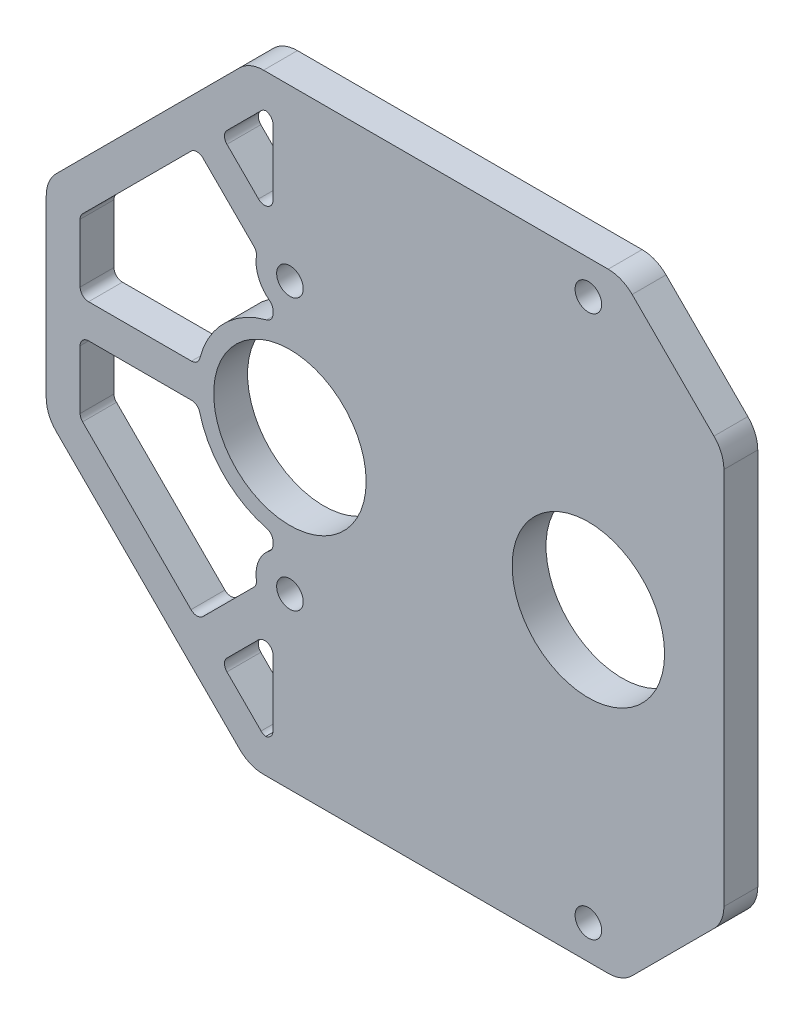
SolidWorks part; units mm, degrees
ref_plane "Front Plane" through (0, 0, 0) normal (0, 0, 1) x (1, 0, 0)
ref_plane "Top Plane" through (0, 0, 0) normal (0, 1, 0) x (1, 0, 0)
ref_plane "Right Plane" through (0, 0, 0) normal (1, 0, 0) x (0, 0, -1)
sketch "Sketch1" plane through (0, 0, 0) normal (0, 0, 1) x (1, 0, 0)
  line L1 (0, 0) -> (127, 0)
  line L2 (0, 0) -> (0, 114.3)
  line L3 (0, 114.3) -> (127, 114.3)
  line L4 (127, 0) -> (127, 114.3)
  circle A0 centre (45.6692, 82.55) radius 2.4892
  circle A1 centre (45.6692, 57.15) radius 14.2875
  circle A2 centre (45.6692, 31.75) radius 2.4892
  circle A3 centre (101.6, 107.95) radius 2.4892
  circle A4 centre (101.6, 57.15) radius 14.2875
  circle A5 centre (101.6, 6.35) radius 2.4892
  dimension "D3" = 25.4
  dimension "D10" = 25.4
  dimension "D12" = 4.9784
  dimension "D13" = 4.9784
  dimension "D14" = 28.575
  dimension "D15" = 28.575
  dimension "D16" = 4.9784
  dimension "D17" = 4.9784
  dimension "D2" = 127
  dimension "D4" = 57.15
  dimension "D5" = 50.8
  dimension "D6" = 50.8
  dimension "D7" = 6.35
  dimension "D8" = 25.4
  dimension "D9" = 25.4
  dimension "D11" = 114.3
  dimension "D18" = 55.9308
extrude "Boss-Extrude1" add sketch "Sketch1" along normal mid plane 6.35
chamfer "Chamfer2" distance 38.1 angle 45 2 edges at (0, 0, 0) (0, 114.3, 0)
chamfer "Chamfer3" distance 19.05 angle 45 2 edges at (127, 0, 0) (127, 114.3, 0)
fillet "Fillet2" radius 6.35 8 edges at (127, 95.25, 0) (107.95, 114.3, 0) (0, 76.2, 0) (0, 38.1, 0) (38.1, 0, 0) (107.95, 0, 0) (127, 19.05, 0) (38.1, 114.3, 0)
sketch "Sketch2" plane through (0, 0, 3.175) normal (0, 0, 1) x (1, 0, 0)
  line L0 (47.9143, 84.7951) -> (26.5569, 106.1525)
  line L1 (48.8442, 82.55) -> (48.8442, 117.6022)
  line L2 (45.6692, 60.325) -> (101.6, 60.325)
  line L3 (45.6692, 60.325) -> (6.35, 60.325)
  line L4 (48.8442, 31.75) -> (48.8442, 82.55)
  line L5 (42.4942, 31.75) -> (42.4942, 6.35)
  line L6 (43.4241, 33.9951) -> (20.6603, 11.2312)
  line L7 (43.4241, 80.3049) -> (22.0667, 101.6623)
  line L8 (45.6692, 31.75) -> (45.6692, 82.55) construction
  line L9 (45.6692, 57.15) -> (101.6, 57.15) construction
  line L10 (101.6, 57.15) -> (120.65, 57.15) construction
  line L11 (45.6692, 82.55) -> (24.3118, 103.9074) construction
  line L12 (45.6692, 57.15) -> (6.35, 57.15) construction
  line L13 (45.6692, 31.75) -> (22.9054, 8.9862) construction
  line L14 (45.6692, 31.75) -> (45.6692, 6.35) construction
  line L15 (45.6692, 82.55) -> (45.6692, 117.6022) construction
  line L16 (120.65, 21.6803) -> (120.65, 92.6197)
  line L17 (120.65, 92.6197) -> (105.3197, 107.95)
  line L18 (105.3197, 107.95) -> (40.7303, 107.95)
  line L19 (40.7303, 107.95) -> (6.35, 73.5697)
  line L20 (6.35, 73.5697) -> (6.35, 40.7303)
  line L21 (6.35, 40.7303) -> (40.7303, 6.35)
  line L22 (40.7303, 6.35) -> (105.3197, 6.35)
  line L23 (105.3197, 6.35) -> (120.65, 21.6803)
  line L24 (120.65, 21.6803) -> (120.65, 92.6197)
  line L25 (120.65, 92.6197) -> (105.3197, 107.95)
  line L26 (105.3197, 107.95) -> (40.7303, 107.95)
  line L27 (40.7303, 107.95) -> (6.35, 73.5697)
  line L28 (6.35, 73.5697) -> (6.35, 40.7303)
  line L29 (6.35, 40.7303) -> (40.7303, 6.35)
  line L30 (40.7303, 6.35) -> (105.3197, 6.35)
  line L31 (105.3197, 6.35) -> (120.65, 21.6803)
  line L32 (42.4942, 82.55) -> (42.4942, 117.6022)
  line L33 (45.6692, 53.975) -> (101.6, 53.975)
  line L34 (45.6692, 53.975) -> (6.35, 53.975)
  line L35 (42.4942, 31.75) -> (42.4942, 82.55)
  line L36 (48.8442, 31.75) -> (48.8442, 6.35)
  line L37 (47.9143, 29.5049) -> (25.1504, 6.7411)
  line L38 (101.6, 53.975) -> (120.65, 53.975)
  line L39 (101.6, 60.325) -> (120.65, 60.325)
  circle A11 centre (45.6692, 57.15) radius 17.4625
  circle A12 centre (45.6692, 82.55) radius 6.35
  circle A13 centre (101.6, 57.15) radius 17.4625
  circle A14 centre (101.6, 107.95) radius 6.35
  circle A15 centre (101.6, 6.35) radius 6.35
  circle A16 centre (45.6692, 31.75) radius 6.35
  circle A17 centre (45.6692, 57.15) radius 14.2875 construction
  circle A18 centre (101.6, 57.15) radius 14.2875 construction
  dimension "D2" = 12.7
  dimension "D3" = 3.175
  dimension "D4" = 3.175
  dimension "D1" = 6.35
  dimension "D5" = 3.175
  dimension "D6" = 3.175
  dimension "D7" = 3.175
  dimension "D8" = 3.175
extrude "Cut-Extrude1" cut sketch "Sketch2" against normal through all contours A16 L35 A11 L34 L28 L29 L6 | A12 L7 L27 L28 L3 A11 L35 | L5 L37 L29 L30 | L0 L32 L26 L27 region at (39.2001, 99.8219, 3.175) region at (23.4963, 75.1509, 3.175) region at (23.4963, 39.1491, 3.175) region at (39.2001, 14.4781, 3.175)
fillet "Fillet3" radius 1.5875 22 edges at (40.7303, 6.35, 0) (42.4942, 24.0849, 0) (42.4942, 6.35, 0) (32.7448, 14.3355, 0) (28.2547, 18.8256, 0) (6.35, 53.975, 0) (28.4978, 53.975, 0) (42.4942, 39.9786, 0) (42.4942, 37.2493, 0) (39.5356, 30.1065, 0) (6.35, 40.7303, 0) (40.7303, 107.95, 0) (42.4942, 107.95, 0) (42.4942, 90.2151, 0) (32.7448, 99.9645, 0) (42.4942, 74.3214, 0) (28.4978, 60.325, 0) (6.35, 73.5697, 0) (28.2547, 95.4744, 0) (39.5356, 84.1935, 0) (42.4942, 77.0507, 0) (6.35, 60.325, 0)
